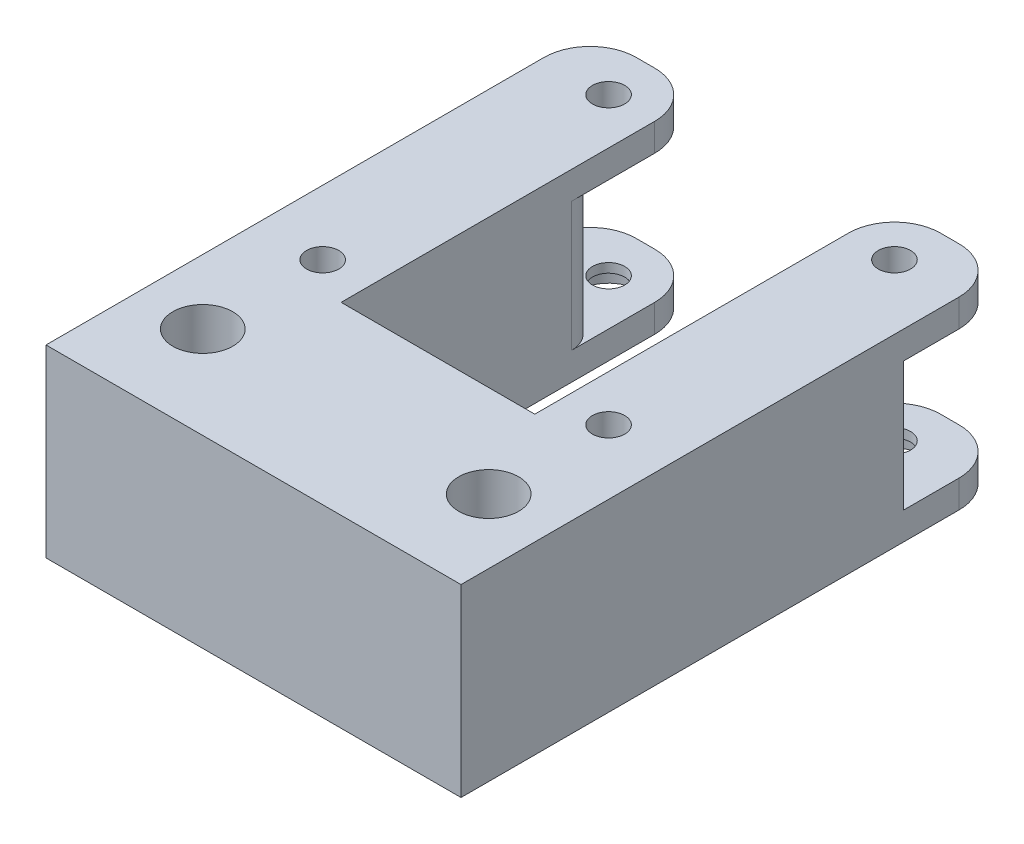
SolidWorks part; units mm, degrees
material "ABS"
ref_plane "Front Plane" through (0, 0, 0) normal (0, 0, 1) x (1, 0, 0)
ref_plane "Top Plane" through (0, 0, 0) normal (0, 1, 0) x (1, 0, 0)
ref_plane "Right Plane" through (0, 0, 0) normal (1, 0, 0) x (0, 0, -1)
sketch "Sketch1" plane through (0, 0, 0) normal (0, 1, 0) x (1, 0, 0)
  line L1 (-22.5, -10) -> (22.5, -10)
  line L2 (-22.5, -10) -> (-22.5, 10)
  line L3 (-22.5, 10) -> (22.5, 10)
  line L4 (22.5, -10) -> (22.5, 10)
  line L5 (-22.5, -10) -> (22.5, 10) construction
  line L6 (-22.5, 10) -> (22.5, -10) construction
  point P0 (0, 0)
  dimension "D1" = 20
  dimension "D2" = 45
extrude "Boss-Extrude1" add sketch "Sketch1" along normal blind 20
sketch "Sketch2" plane through (0, 0, -10) normal (0, 0, -1) x (-1, 0, 0)
  line L0 (-22.5, 20) -> (-22.5, 0) construction
  line L1 (-22.5, 20) -> (-10.5, 20)
  line L2 (-22.5, 20) -> (-22.5, 0)
  line L3 (-22.5, 0) -> (-10.5, 0)
  line L4 (-10.5, 20) -> (-10.5, 0)
  line L5 (-22.5, 20) -> (22.5, 20) construction
  line L11 (22.5, 20) -> (10.5, 20)
  line L12 (22.5, 20) -> (22.5, 0)
  line L13 (22.5, 0) -> (10.5, 0)
  line L14 (10.5, 20) -> (10.5, 0)
  dimension "D1" = 20
  dimension "D2" = 12
  dimension "D3" = 12
  dimension "D4" = 20
extrude "Boss-Extrude2" add sketch "Sketch2" along normal blind 40
sketch "Sketch3" plane through (0, 20, 0) normal (0, 1, 0) x (1, 0, 0)
  line L1 (22.5, -10) -> (22.5, 50) construction
  line L2 (10.5, 10) -> (-10.5, 10) construction
  circle A0 centre (15.5, 44) radius 1.75
  circle A1 centre (15.5, 13) radius 1.75
  circle A2 centre (-15.5, 13) radius 1.75
  circle A3 centre (-15.5, 44) radius 1.75
  dimension "D1" = 3.5
  dimension "D3" = 3.5
  dimension "D6" = 3.5
  dimension "D7" = 3.5
  dimension "D2" = 7
  dimension "D4" = 3
  dimension "D5" = 31
  dimension "D8" = 31
extrude "Cut-Extrude1" cut sketch "Sketch3" against normal through all
sketch "Sketch4" plane through (0, 20, 0) normal (0, 1, 0) x (1, 0, 0)
  line L0 (22.5, -10) -> (22.5, 50) construction
  line L1 (-22.5, 50) -> (-22.5, -10) construction
  circle A0 centre (-15.5, 0) radius 1.75
  circle A1 centre (15.5, 0) radius 1.75
  dimension "D1" = 3.5
  dimension "D2" = 3.5
  dimension "D3" = 7
  dimension "D4" = 7
extrude "Cut-Extrude2" cut sketch "Sketch4" against normal blind 25
hole_wizard "CBORE for M3 Hex Socket Head Cap Screw1" positions "Sketch5" profile "Sketch6" counterbore size "M3" standard "ISO" end condition through all
sketch "Sketch5" plane through (0, 20, 0) normal (0, 1, 0) x (1, 0, 0)
  point P0 (15.5, 0)
  point P3 (-15.5, 0)
sketch "Sketch6" plane through (15.5, 20, 0) normal (1, 0, 0) x (0, 0, 1)
  line L0 (0, 0) -> (0, 20)
  line L1 (0, 20) -> (1.75, 20)
  line L3 (1.75, 20) -> (1.75, 11.4)
  line L4 (1.75, 11.4) -> (3.25, 11.4)
  line L5 (3.25, 11.4) -> (3.25, 0)
  line L7 (3.25, 0) -> (0, 0)
  line L11 (0, -6.35) -> (0, 107.95) construction
  dimension "Thru Hole Dia." = 3.5
  dimension "Thru Hole Depth" = 20
  dimension "C'Bore Dia." = 6.5
  dimension "C'Bore Depth" = 11.4
hole_wizard "CBORE for M3 Hex Socket Head Cap Screw2" positions "Sketch7" profile "Sketch8" counterbore size "M3" standard "ISO" end condition through all
sketch "Sketch7" plane through (0, 0, 0) normal (0, -1, 0) x (-1, 0, 0)
  point P0 (15.5, 44)
  point P3 (15.5, 13)
  point P6 (-15.5, 13)
  point P9 (-15.5, 44)
sketch "Sketch8" plane through (-15.5, 0, -44) normal (1, 0, 0) x (0, 0, -1)
  line L0 (0, 0) -> (0, 20)
  line L1 (0, 20) -> (1.75, 20)
  line L3 (1.75, 20) -> (1.75, 2)
  line L4 (1.75, 2) -> (3.25, 2)
  line L5 (3.25, 2) -> (3.25, 0)
  line L7 (3.25, 0) -> (0, 0)
  line L11 (0, -6.35) -> (0, 107.95) construction
  dimension "Thru Hole Dia." = 3.5
  dimension "Thru Hole Depth" = 20
  dimension "C'Bore Dia." = 6.5
  dimension "C'Bore Depth" = 2
hole_wizard "CBORE for M3 Pan Head Screw1" positions "Sketch11" profile "Sketch12" counterbore size "M3" standard "JIS" end condition through all
sketch "Sketch11" plane through (0, 0, 0) normal (0, -1, 0) x (-1, 0, 0)
  point P0 (-15.5, 13)
  point P3 (15.5, 13)
sketch "Sketch12" plane through (15.5, 0, -13) normal (1, 0, 0) x (0, 0, -1)
  line L0 (0, 0) -> (0, 20)
  line L1 (0, 20) -> (1.75, 20)
  line L3 (1.75, 20) -> (1.75, 12.4)
  line L4 (1.75, 12.4) -> (3.25, 12.4)
  line L5 (3.25, 12.4) -> (3.25, 0)
  line L7 (3.25, 0) -> (0, 0)
  line L11 (0, -6.35) -> (0, 107.95) construction
  dimension "Thru Hole Dia." = 3.5
  dimension "Thru Hole Depth" = 20
  dimension "C'Bore Dia." = 6.5
  dimension "C'Bore Depth" = 12.4
sketch "Sketch9" plane through (22.5, 0, 0) normal (1, 0, 0) x (0, 0, -1)
  line L0 (50, 20) -> (50, 0) construction
  line L1 (50, 17) -> (38, 17)
  line L2 (50, 17) -> (50, 3)
  line L3 (50, 3) -> (38, 3)
  line L4 (38, 17) -> (38, 3)
  line L5 (-10, 20) -> (50, 20) construction
  line L6 (-10, 0) -> (50, 0) construction
  dimension "D1" = 12
  dimension "D2" = 3
  dimension "D3" = 3
extrude "Cut-Extrude3" cut sketch "Sketch9" against normal through all and the other way through all
sketch "Sketch10" plane through (0, 0, -50) normal (0, 0, -1) x (-1, 0, 0)
  line L0 (22.5, 17) -> (10.5, 17) construction
  line L1 (-22.5, 3) -> (-10.5, 3)
  line L2 (-22.5, 3) -> (-22.5, 0)
  line L3 (-22.5, 0) -> (-10.5, 0)
  line L4 (-10.5, 3) -> (-10.5, 0)
  line L5 (10.5, 3) -> (22.5, 3)
  line L6 (10.5, 3) -> (10.5, 0)
  line L7 (10.5, 0) -> (22.5, 0)
  line L8 (22.5, 3) -> (22.5, 0)
  line L9 (-22.5, 20) -> (-10.5, 20)
  line L10 (-22.5, 20) -> (-22.5, 17)
  line L11 (-22.5, 17) -> (-10.5, 17)
  line L12 (-10.5, 20) -> (-10.5, 17)
  line L13 (10.5, 20) -> (22.5, 20)
  line L14 (10.5, 20) -> (10.5, 17)
  line L15 (10.5, 17) -> (22.5, 17)
  line L16 (22.5, 20) -> (22.5, 17)
extrude "Cut-Extrude5" cut sketch "Sketch10" against normal blind 1
fillet "Fillet2" radius 5 8 edges at (-10.5, 1.5, -49) (10.5, 1.5, -49) (-10.5, 18.5, -49) (10.5, 18.5, -49) (-22.5, 18.5, -49) (-22.5, 1.5, -49) (22.5, 1.5, -49) (22.5, 18.5, -49)
fillet "Fillet5" radius 3 2 edges at (-10.5, 10, -38) (10.5, 10, -38)
